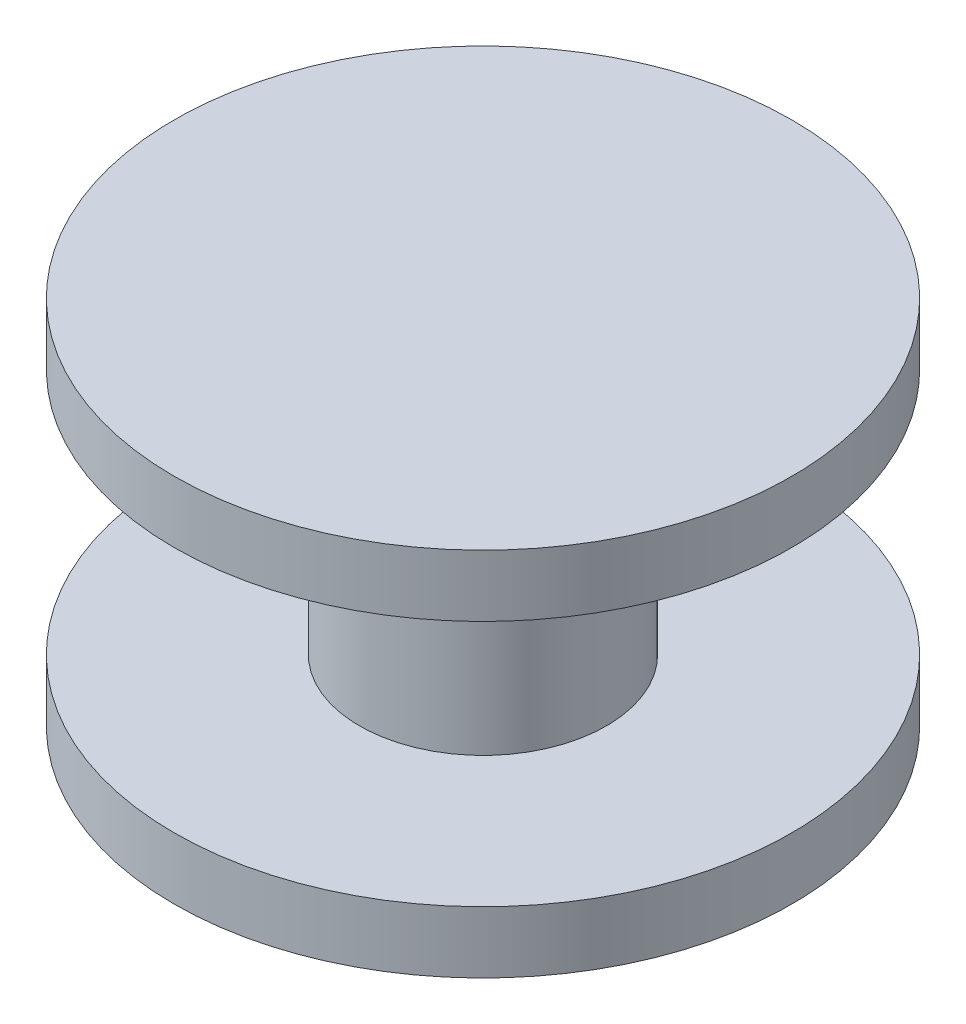
SolidWorks part; units mm, degrees
ref_plane "Front Plane" through (0, 0, 0) normal (0, 0, 1) x (1, 0, 0)
ref_plane "Top Plane" through (0, 0, 0) normal (0, 1, 0) x (1, 0, 0)
ref_plane "Right Plane" through (0, 0, 0) normal (1, 0, 0) x (0, 0, -1)
sketch "Sketch1" plane through (0, 0, 0) normal (0, 0, 1) x (1, 0, 0)
  line L0 (0, 0) -> (0, 19.05)
  line L1 (0, 19.05) -> (12.7, 19.05) construction
  line L2 (12.7, 19.05) -> (12.7, 6.35)
  line L3 (12.7, 6.35) -> (31.75, 6.35)
  line L4 (31.75, 6.35) -> (31.75, 0)
  line L5 (31.75, 0) -> (0, 0)
  line L6 (0, 19.05) -> (0, 38.1)
  line L7 (0, 38.1) -> (31.75, 38.1)
  line L8 (31.75, 38.1) -> (31.75, 31.75)
  line L9 (31.75, 31.75) -> (12.7, 31.75)
  line L10 (12.7, 31.75) -> (12.7, 19.05)
  dimension "D1" = 6.35
  dimension "D2" = 19.05
  dimension "D3" = 31.75
  dimension "D4" = 12.7
revolve "Revolve3" add sketch "Sketch1" angle 360 about L6
